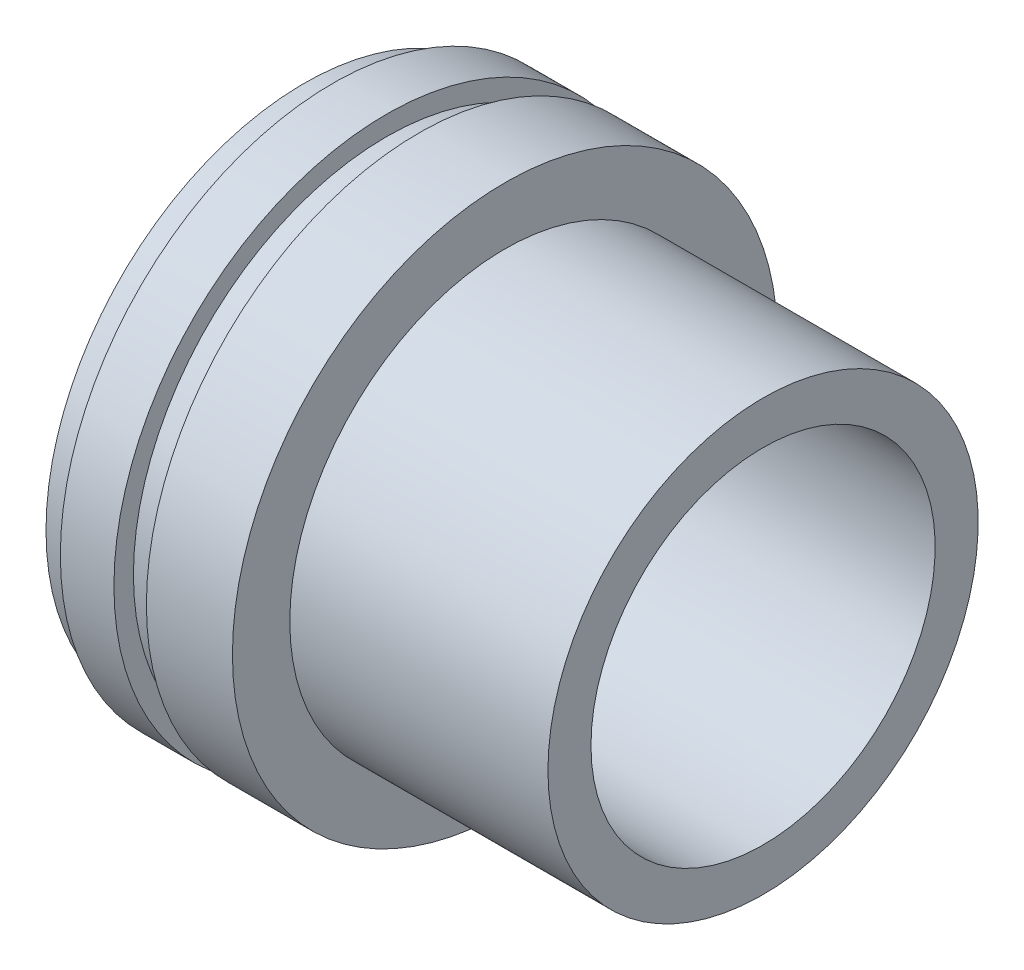
SolidWorks part; units mm, degrees
material "Epoxy, Unfilled"
ref_plane "Front Plane" through (0, 0, 0) normal (0, 0, 1) x (1, 0, 0)
ref_plane "Top Plane" through (0, 0, 0) normal (0, 1, 0) x (1, 0, 0)
ref_plane "Right Plane" through (0, 0, 0) normal (1, 0, 0) x (0, 0, -1)
sketch "Sketch1" plane through (0, 0, 0) normal (0, 0, 1) x (1, 0, 0)
  line L0 (0, 0) -> (0, 9.525)
  line L2 (0, 9.525) -> (25.4, 9.525)
  line L4 (25.4, 9.525) -> (38.1, 22.225)
  line L5 (44.45, 0) -> (44.45, 12.7)
  line L6 (38.1, 22.225) -> (101.6, 22.225)
  line L9 (44.45, 12.7) -> (101.6, 12.7)
  line L10 (101.6, 12.7) -> (101.6, 22.225)
  line L11 (0, 0) -> (18.2118, 0)
  line L12 (0, 60.325) -> (98.3752, 60.325) construction
  line L13 (44.45, 0) -> (25.4, 0)
  line L14 (25.4, 0) -> (25.4, 4.318)
  line L15 (25.4, 4.318) -> (18.2118, 4.318)
  line L16 (18.2118, 4.318) -> (18.2118, 0)
  line L17 (0, 0) -> (6.35, 0)
  line L18 (6.35, 0) -> (6.35, 3.175)
  line L19 (6.35, 3.175) -> (0, 3.175)
  dimension "D1" = 57.15
  dimension "D2" = 25.4
  dimension "D3" = 60.325
  dimension "D4" = 9.525
  dimension "D5" = 12.7
  dimension "D6" = 45
  dimension "D7" = 63.5
  dimension "D8" = 44.45
  dimension "D9" = 12.7
  dimension "D10" = 4.318
  dimension "D11" = 7.1882
  dimension "D12" = 19.05
revolve "Revolve1" add sketch "Sketch1" angle 360 about L12 region at (50.5461, 12.8155, 0)
